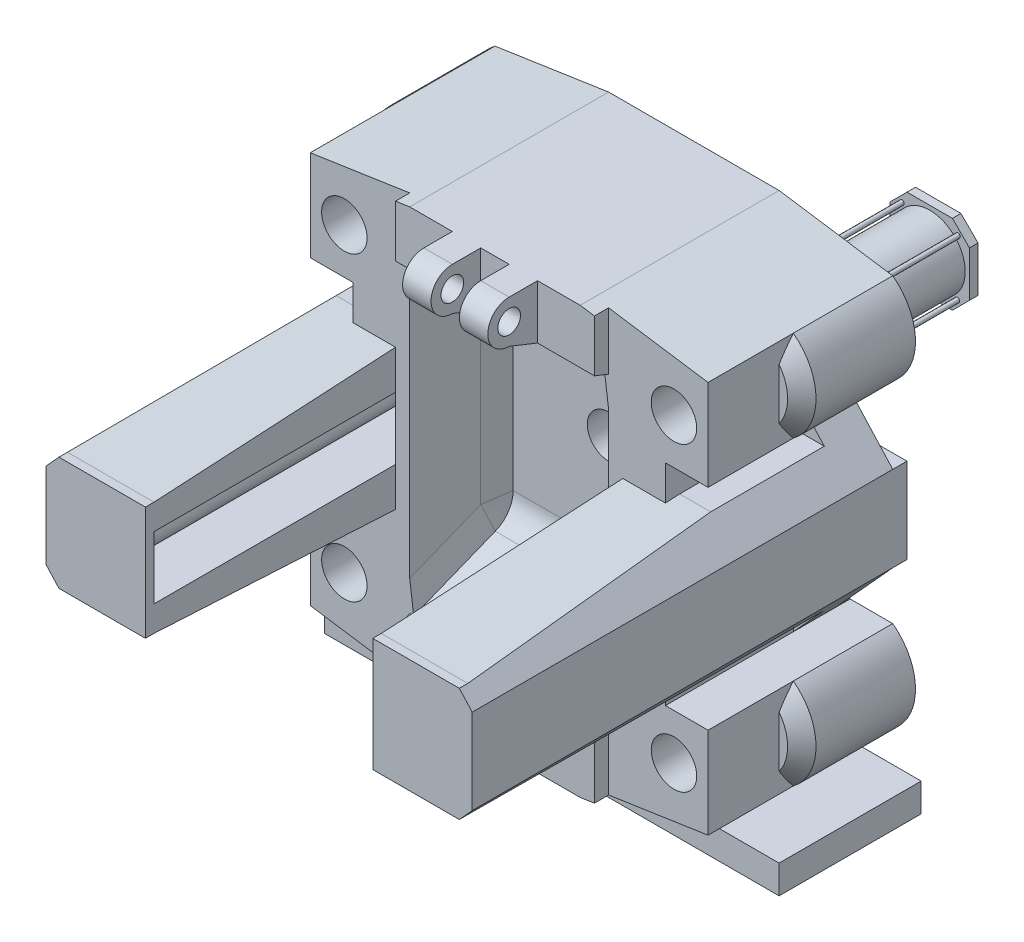
SolidWorks part; units mm, degrees
material "Malleable Cast Iron"
ref_plane "Front Plane" through (0, 0, 0) normal (0, 0, 1) x (1, 0, 0)
ref_plane "Top Plane" through (0, 0, 0) normal (0, 1, 0) x (1, 0, 0)
ref_plane "Right Plane" through (0, 0, 0) normal (1, 0, 0) x (0, 0, -1)
sketch "Sketch1" plane through (0, 0, 0) normal (0, 0, 1) x (1, 0, 0)
  line L1 (-700, 750) -> (700, 750)
  line L2 (-700, 750) -> (-700, -750)
  line L3 (-700, -750) -> (700, -750)
  line L4 (700, 750) -> (700, -750)
  line L5 (0, -750) -> (0, 750) construction
  line L6 (-700, 0) -> (700, 0) construction
  point P0 (0, 0)
extrude "Boss-Extrude1" add sketch "Sketch1" along normal blind 800
sketch "Sketch2" plane through (0, 0, 800) normal (0, 0, 1) x (1, 0, 0)
  line L0 (-700, 750) -> (-700, -750) construction
  circle A0 centre (-580, 530) radius 80
  circle A1 centre (580, 530) radius 80
  circle A2 centre (580, -530) radius 80
  circle A3 centre (-580, -530) radius 80
  point P4 (-700, 0)
  dimension "D1" = 1160
  dimension "D2" = 580
  dimension "D3" = 530
extrude "Cut-Extrude1" cut sketch "Sketch2" against normal blind 800
sketch "Sketch3" plane through (0, 0, 0) normal (0, 0, -1) x (-1, 0, 0)
  circle A0 centre (-580, 530) radius 80
  circle A1 centre (580, 530) radius 80
  circle A2 centre (580, -530) radius 80
  circle A3 centre (-580, -530) radius 80
  circle A4 centre (-580, -530) radius 200
  circle A5 centre (-580, 530) radius 200
  circle A6 centre (580, 530) radius 200
  circle A7 centre (580, -530) radius 200
extrude "Boss-Extrude2" add sketch "Sketch3" against normal blind 400
chamfer "Chamfer1" distance 50 angle 45 1 edges at (-780, 530, 400)
chamfer "Chamfer2" distance 50 angle 45 3 edges at (780, -530, 400) (780, 530, 400) (-780, -530, 400)
sketch "Sketch4" plane through (0, 0, 0) normal (0, 0, -1) x (-1, 0, 0)
  line L0 (-700, 750) -> (-300, 750)
  line L1 (-700, 750) -> (700, 750) construction
  line L2 (-300, 750) -> (-700, 690)
  line L3 (-700, 690) -> (-700, 750)
extrude "Cut-Extrude2" cut sketch "Sketch4" against normal blind 960
ref_plane "Plane1" through (0, 0, 0) normal (-1, 0, 0) x (0, 0, 1)
ref_plane "Plane2" through (0, 0, 0) normal (0, -1, 0) x (-1, 0, 0)
mirror "Mirror1" about plane through (0, 0, 0) normal (-1, 0, 0) of "Cut-Extrude2"
mirror "Mirror2" about plane through (0, 0, 0) normal (0, -1, 0) of "Mirror1"
sketch "Sketch5" plane through (0, 0, 800) normal (0, 0, 1) x (1, 0, 0)
  line L1 (-350, 795.5511) -> (-797.0636, 795.5511)
  line L2 (-350, 795.5511) -> (-350, -826.0958)
  line L3 (-350, -826.0958) -> (-797.0636, -826.0958)
  line L4 (-797.0636, 795.5511) -> (-797.0636, -826.0958)
  dimension "D1" = 350
extrude "Cut-Extrude3" cut sketch "Sketch5" against normal blind 150
mirror "Mirror3" about plane through (0, 0, 0) normal (-1, 0, 0) of "Cut-Extrude3"
sketch "Sketch6" plane through (0, 0, 650) normal (0, 0, 1) x (1, 0, 0)
  line L0 (-700, -690) -> (-700, 690) construction
  line L1 (-700, 150) -> (-400, 150)
  line L2 (-700, 150) -> (-700, -150)
  line L3 (-700, -150) -> (-400, -150)
  line L4 (-400, 150) -> (-400, -150)
  dimension "D1" = 300
  dimension "D2" = 150
  dimension "D3" = 300
extrude "Cut-Extrude4" cut sketch "Sketch6" against normal blind 975
mirror "Mirror4" about plane through (0, 0, 0) normal (-1, 0, 0) of "Cut-Extrude4"
sketch "Sketch7" plane through (0, 0, 650) normal (0, 0, 1) x (1, 0, 0)
  line L1 (-700, 370) -> (-550, 370)
  line L2 (-700, 370) -> (-700, -370)
  line L3 (-700, -370) -> (-550, -370)
  line L4 (-550, 370) -> (-550, -370)
extrude "Cut-Extrude5" cut sketch "Sketch7" against normal blind 975
mirror "Mirror5" about plane through (0, 0, 0) normal (-1, 0, 0) of "Cut-Extrude5"
sketch "Sketch8" plane through (0, 0, 0) normal (0, 0, -1) x (-1, 0, 0)
  line L1 (400, 150) -> (750, 150)
  line L2 (400, 150) -> (400, -150)
  line L3 (400, -150) -> (750, -150)
  line L4 (750, 150) -> (750, -150)
extrude "Boss-Extrude3" add sketch "Sketch8" against normal blind 100
sketch "Sketch9" plane through (0, 0, 100) normal (0, 0, 1) x (1, 0, 0)
  line L1 (-400, 150) -> (-710, 150)
  line L2 (-400, 150) -> (-400, 110)
  line L3 (-400, 110) -> (-710, 110)
  line L4 (-750, 150) -> (-750, -150)
  line L8 (-750, 150) -> (-710, 150)
  line L9 (-710, -110) -> (-710, 110)
  line L10 (-400, -150) -> (-750, -150)
  line L11 (-400, -150) -> (-400, -110)
  line L12 (-400, -110) -> (-710, -110)
extrude "Boss-Extrude4" add sketch "Sketch9" along normal blind 100
sketch "Sketch10" plane through (0, 0, 200) normal (0, 0, 1) x (1, 0, 0)
  line L0 (-750, 150) -> (-550, 370)
  line L1 (-550, 370) -> (-550, 150)
  line L2 (-550, 150) -> (-750, 150)
extrude "Boss-Extrude5" add sketch "Sketch10" against normal blind 150
mirror "Mirror6" about plane through (0, 0, 0) normal (0, -1, 0) of "Boss-Extrude5"
mirror "Mirror7" about plane through (0, 0, 0) normal (-1, 0, 0) of "Boss-Extrude4", "Boss-Extrude3", "Mirror6"
sketch "Sketch11" plane through (0, 0, 100) normal (0, 0, 1) x (1, 0, 0)
  circle A0 centre (-552.5817, 0) radius 110
extrude "Boss-Extrude9" add sketch "Sketch11" along normal blind 50 separate body
sketch "Sketch12" plane through (0, 0, 150) normal (0, 0, 1) x (1, 0, 0)
  circle A0 centre (-552.5817, 0) radius 60
extrude "Boss-Extrude10" add sketch "Sketch12" along normal blind 1350 separate body
pattern_linear "LPattern1" count 2 spacing 1107 along (1, 0, 0) of "Boss-Extrude10", "Boss-Extrude9"
sketch "Sketch14" plane through (0, 0, 0) normal (-1, 0, 0) x (0, 0, 1)
  line L0 (800, 600) -> (800, -600)
  line L1 (800, -742.5) -> (800, 742.5) construction
  line L4 (300, -400) -> (300, 400)
  line L5 (300, 400) -> (800, 600)
  line L6 (300, -400) -> (800, -600)
extrude "Cut-Extrude7" cut sketch "Sketch14" against normal up to surface and the other way up to surface up to face at (350, 0, 725) other way up to face at (-350, 0, 725)
fillet "Fillet3" radius 100 2 edges at (0, -400, 300) (0, 400, 300)
chamfer "Chamfer3" distance 100 angle 8 5 edges at (-350, -482.5722, 506.4305) (-350, -388.3596, 317.1933) (-350, 0, 300) (-350, 388.3596, 317.1933) (-350, 482.5722, 506.4305) first distance on face at (-350, 0, 432.8746)
chamfer "Chamfer4" distance 100 angle 8 5 edges at (350, -482.5722, 506.4305) (350, -388.3596, 317.1933) (350, 0, 300) (350, 388.3596, 317.1933) (350, 482.5722, 506.4305) first distance on face at (350, 0, 432.8746)
sketch "Sketch15" plane through (-350, 0, 0) normal (-1, 0, 0) x (0, 0, 1)
  line L0 (800, 600) -> (800, 750)
  arc A0 (800, 600) -> (800, 750) centre (800, 675) ccw
extrude "Boss-Extrude11" add sketch "Sketch15" against normal blind 700
sketch "Sketch16" plane through (0, 0, 800) normal (0, 0, -1) x (-1, 0, 0)
  line L3 (-350, 742.5) -> (-300, 750)
  line L4 (-300, 750) -> (-350, 750)
  line L5 (-350, 750) -> (-350, 742.5)
  line L6 (-350, 742.5) -> (-300, 750)
  line L7 (-300, 750) -> (-350, 750)
  line L8 (-350, 750) -> (-350, 742.5)
  line L9 (350, 750) -> (300, 750)
  line L10 (300, 750) -> (350, 742.5)
  line L11 (350, 742.5) -> (350, 750)
  line L12 (350, 750) -> (300, 750)
  line L13 (300, 750) -> (350, 742.5)
  line L14 (350, 742.5) -> (350, 750)
  dimension "D1" = 0
  dimension "D2" = 0
extrude "Cut-Extrude8" cut sketch "Sketch16" against normal blind 700
mirror "Mirror28" about plane through (0, 0, 0) normal (0, -1, 0) of "Boss-Extrude11", "Cut-Extrude8"
sketch "Sketch19" plane through (-350, 0, 0) normal (-1, 0, 0) x (0, 0, 1)
  circle A0 centre (800, 675) radius 40
extrude "Cut-Extrude10" cut sketch "Sketch19" against normal blind 783
mirror "Mirror31" about plane through (0, 0, 0) normal (0, -1, 0) of "Cut-Extrude10"
sketch "Sketch20" plane through (0, 0, 0) normal (0, 0, -1) x (-1, 0, 0)
  line L0 (0, -750) -> (0, -900)
  line L1 (300, -750) -> (-300, -750) construction
  line L2 (0, -165) -> (0, 165) construction
  line L3 (0, -900) -> (800, -900)
  line L4 (800, -900) -> (800, -800)
  line L5 (500, -720) -> (580, -800)
  line L6 (580, -800) -> (800, -800)
  line L7 (700, -690) -> (300, -750) construction
  line L8 (500, -720) -> (0, -750)
extrude "Boss-Extrude12" add sketch "Sketch20" against normal blind 500
mirror "Mirror32" about plane through (0, 0, 0) normal (-1, 0, 0) of "Boss-Extrude12"
sketch "Sketch22" plane through (0, 0, 200) normal (0, 0, 1) x (1, 0, 0)
  line L0 (-400, 150) -> (-400, 250)
  line L1 (-400, 250) -> (-659.0909, 250)
  line L2 (-400, -150) -> (-400, -250)
  line L3 (-400, -250) -> (-659.0909, -250)
  line L12 (-400, 110) -> (-400, 150)
  line L13 (-400, 150) -> (-550, 150)
  line L14 (-550, 150) -> (-550, 370)
  line L15 (-550, 370) -> (-750, 150)
  line L16 (-750, 150) -> (-750, -150)
  line L17 (-750, -150) -> (-550, -370)
  line L18 (-550, -370) -> (-550, -150)
  line L19 (-550, -150) -> (-400, -150)
  line L20 (-400, -150) -> (-400, -110)
  line L21 (-400, -110) -> (-710, -110)
  line L22 (-710, -110) -> (-710, 110)
  line L23 (-710, 110) -> (-400, 110)
  line L24 (-400, 110) -> (-400, 150)
  line L27 (-659.0909, 250) -> (-750, 150)
  line L28 (-750, 150) -> (-750, -150)
  line L29 (-750, -150) -> (-659.0909, -250)
  line L32 (-400, -150) -> (-400, -110)
  line L33 (-400, -110) -> (-710, -110)
  line L34 (-710, -110) -> (-710, 110)
  line L35 (-710, 110) -> (-400, 110)
  dimension "D1" = 0
extrude "Boss-Extrude14" add sketch "Sketch22" along normal blind 1300
mirror "Mirror36" about plane through (0, 0, 0) normal (-1, 0, 0) of "Boss-Extrude14"
chamfer "Chamfer9" distance 900 distance2 50 1 edges at (-529.5455, 250, 1500) first distance on face at (-536.3636, 250, 783.3333)
chamfer "Chamfer10" distance 50 distance2 900 1 edges at (529.5455, 250, 1500) first distance on face at (583.8182, 0, 1500)
chamfer "Chamfer11" distance 900 distance2 50 1 edges at (-529.5455, -250, 1500) first distance on face at (-536.3636, -250, 783.3333)
chamfer "Chamfer12" distance 50 distance2 900 1 edges at (529.5455, -250, 1500) first distance on face at (588.3636, -10, 1500)
sketch "Sketch24" plane through (0, 0, 1500) normal (0, 0, 1) x (1, 0, 0)
  line L0 (-400, 110) -> (-400, -110)
  line L10 (-750, -150) -> (-704.5455, -200)
  line L11 (-704.5455, -200) -> (-400, -200)
  line L12 (-400, -200) -> (-400, -110)
  line L13 (-400, -110) -> (-710, -110)
  line L14 (-710, -110) -> (-710, 110)
  line L15 (-710, 110) -> (-400, 110)
  line L16 (-400, 110) -> (-400, 200)
  line L17 (-400, 200) -> (-704.5455, 200)
  line L18 (-704.5455, 200) -> (-750, 150)
  line L19 (-750, 150) -> (-750, -150)
  line L20 (-750, -150) -> (-704.5455, -200)
  line L21 (-704.5455, -200) -> (-400, -200)
  line L22 (-400, -200) -> (-400, -110)
  line L26 (-400, 110) -> (-400, 200)
  line L27 (-400, 200) -> (-704.5455, 200)
  line L28 (-704.5455, 200) -> (-750, 150)
  line L29 (-750, 150) -> (-750, -150)
  dimension "D1" = 0
extrude "Boss-Extrude16" add sketch "Sketch24" along normal blind 30
mirror "Mirror40" about plane through (0, 0, 0) normal (-1, 0, 0) of "Boss-Extrude16"
sketch "Sketch25" plane through (0, 0, 0) normal (-1, 0, 0) x (0, 0, 1)
  line L0 (650, 370) -> (650, 690) construction
  line L1 (700, 540) -> (964.8568, 540)
  line L2 (700, 540) -> (700, 874.6902)
  line L3 (700, 874.6902) -> (964.8568, 874.6902)
  line L4 (964.8568, 540) -> (964.8568, 874.6902)
  dimension "D1" = 50
extrude "Cut-Extrude11" cut sketch "Sketch25" against normal blind 50 and the other way blind 50
sketch "Sketch26" plane through (50, 0, 0) normal (-1, 0, 0) x (0, 0, 1)
  line L3 (700, 750) -> (700, 560)
  line L4 (700, 560) -> (800, 600)
  line L5 (800, 750) -> (700, 750)
  line L6 (700, 750) -> (700, 560)
  line L7 (700, 560) -> (800, 600)
  line L8 (800, 750) -> (700, 750)
  arc A1 (800, 600) -> (800, 750) centre (800, 675) ccw
  arc A2 (800, 600) -> (800, 750) centre (800, 675) ccw
  dimension "D1" = 0
extrude "Cut-Extrude12" cut sketch "Sketch26" against normal blind 268 from offset 100 offset against normal yes
mirror "Mirror41" about plane through (0, 0, 0) normal (-1, 0, 0) of "Cut-Extrude12"
mirror "Mirror42" about plane through (0, 0, 0) normal (0, -1, 0) of "Cut-Extrude11", "Cut-Extrude12", "Mirror41"
sketch "Sketch27" plane through (0, 0, 0) normal (0, 0, -1) x (-1, 0, 0)
  circle A0 centre (0, 0) radius 75
extrude "Cut-Extrude13" cut sketch "Sketch27" against normal blind 1334
sketch "Sketch28" plane through (0, 0, 0) normal (0, 0, -1) x (-1, 0, 0)
  circle A1 centre (0, 0) radius 180
  circle A2 centre (0, 0) radius 50
extrude "Boss-Extrude17" add sketch "Sketch28" along normal blind 30
sketch "Sketch29" plane through (0, 0, -30) normal (0, 0, -1) x (-1, 0, 0)
  circle A0 centre (0, 0) radius 100
  circle A1 centre (0, 0) radius 125
extrude "Boss-Extrude18" add sketch "Sketch29" along normal blind 800
sketch "Sketch30" plane through (0, 0, -830) normal (0, 0, -1) x (-1, 0, 0)
  line L1 (-140, 140) -> (140, 140)
  line L2 (-140, 140) -> (-140, -140)
  line L3 (-140, -140) -> (140, -140)
  line L4 (140, 140) -> (140, -140)
  line L5 (-140, 140) -> (140, -140) construction
  line L6 (-140, -140) -> (140, 140) construction
  point P0 (0, 0)
extrude "Boss-Extrude19" add sketch "Sketch30" along normal blind 30
chamfer "Chamfer13" distance 60 angle 45 4 edges at (140, -140, -845) (140, 140, -845) (-140, -140, -845) (-140, 140, -845)
sketch "Sketch31" plane through (0, 0, -830) normal (0, 0, 1) x (1, 0, 0)
  circle A0 centre (99.6014, 97.6299) radius 8
extrude "Boss-Extrude20" add sketch "Sketch31" along normal blind 845
ref_axis "Axis1" through (0, 0, -830) along (0, 0, 1)
pattern_circular "CirPattern1" count 4 over 360 about axis through (0, 0, -830) along (0, 0, 1) of "Boss-Extrude20"
